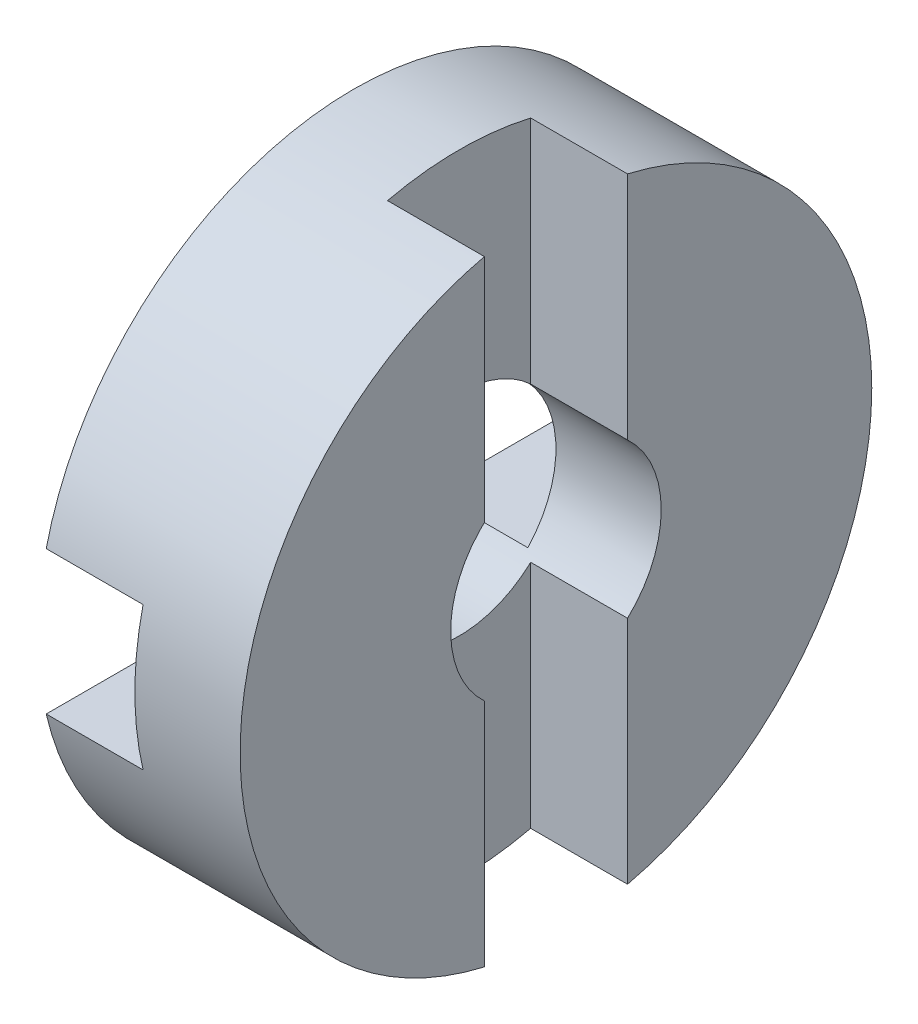
SolidWorks part; units mm, degrees
ref_plane "Front Plane" through (0, 0, 0) normal (0, 0, 1) x (1, 0, 0)
ref_plane "Top Plane" through (0, 0, 0) normal (0, 1, 0) x (1, 0, 0)
ref_plane "Right Plane" through (0, 0, 0) normal (1, 0, 0) x (0, 0, -1)
ref_plane "Plane1" through (0, 0, 0) normal (0, 0, 1) x (1, 0, 0)
sketch "Sketch1" plane through (0, 0, 0) normal (0, 0, 1) x (1, 0, 0)
  line L0 (0, 7.5) -> (0, 2.5)
  line L1 (0, 2.5) -> (4.8, 2.5)
  line L2 (4.8, 2.5) -> (4.8, 7.5)
  line L3 (4.8, 7.5) -> (0, 7.5)
  line L4 (4.8, 0) -> (0, 0) construction
revolve "Revolve1" add sketch "Sketch1" angle 360 about L4 reverse direction yes
ref_plane "Plane2" through (0, 0, 0) normal (0, 0, 1) x (1, 0, 0)
sketch "Sketch2" plane through (0, 0, 0) normal (0, 0, 1) x (1, 0, 0)
  line L0 (0, -1.7) -> (2.3, -1.7)
  line L1 (2.3, -1.7) -> (2.3, 1.7)
  line L2 (2.3, 1.7) -> (0, 1.7)
  line L3 (0, 1.7) -> (0, -1.7)
extrude "Cut-Extrude1" cut sketch "Sketch2" against normal blind 7.5 and the other way blind 7.5
ref_plane "Plane3" through (0, 0, 0) normal (0, 1, 0) x (-1, 0, 0)
sketch "Sketch3" plane through (0, 0, 0) normal (0, 1, 0) x (-1, 0, 0)
  line L0 (-2.5, -1.7) -> (-2.5, 1.7)
  line L1 (-2.5, 1.7) -> (-4.8, 1.7)
  line L2 (-4.8, 1.7) -> (-4.8, -1.7)
  line L3 (-4.8, -1.7) -> (-2.5, -1.7)
extrude "Cut-Extrude2" cut sketch "Sketch3" against normal blind 7.5 and the other way blind 7.5
